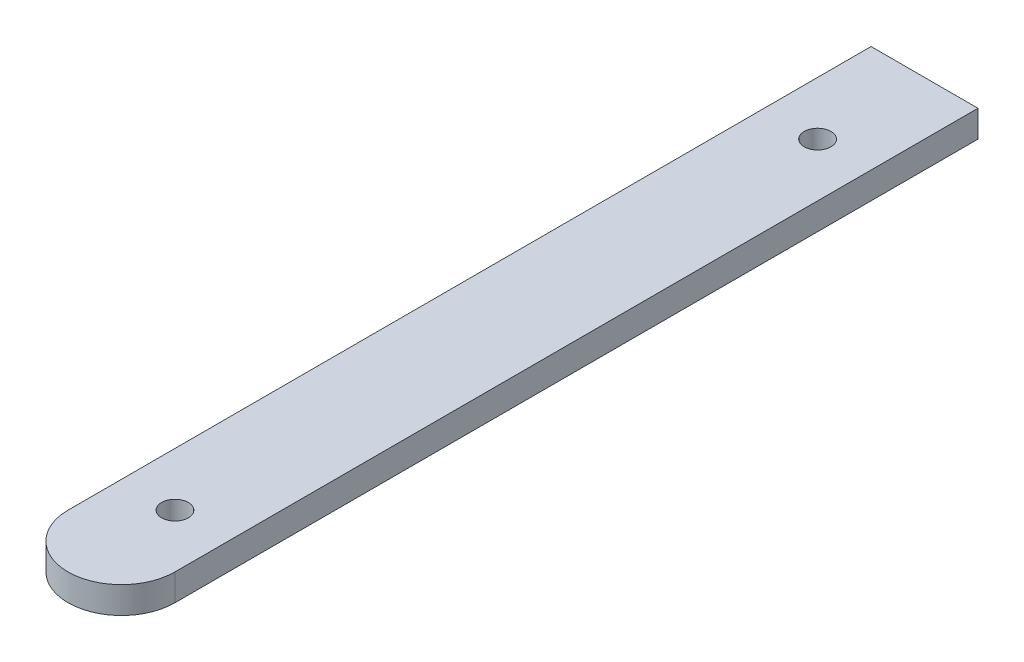
SolidWorks part; units mm, degrees
ref_plane "Front Plane" through (0, 0, 0) normal (0, 0, 1) x (1, 0, 0)
ref_plane "Top Plane" through (0, 0, 0) normal (0, 1, 0) x (1, 0, 0)
ref_plane "Right Plane" through (0, 0, 0) normal (1, 0, 0) x (0, 0, -1)
sketch "Sketch1" plane through (0, 0, 0) normal (0, 1, 0) x (1, 0, 0)
  line L1 (-6.4034, 28.0681) -> (18.9966, 28.0681)
  line L2 (-6.4034, 28.0681) -> (-6.4034, -175.3859)
  line L3 (-6.4034, -175.3859) -> (18.9966, -175.3859)
  line L4 (18.9966, 28.0681) -> (18.9966, -175.3859)
  circle A0 centre (6.2966, 2.6681) radius 3.175
  circle A1 centre (6.2966, -149.9859) radius 3.175
  point P8 (0, 0)
  dimension "D2" = 6.35
  dimension "D1" = 25.4
  dimension "D3" = 12.7
  dimension "D4" = 152.654
  dimension "D5" = 25.4
  dimension "D6" = 203.454
extrude "Boss-Extrude1" add sketch "Sketch1" along normal blind 6.35
fillet "Fillet1" 2 edges at (-6.4034, 3.175, 175.3859) (18.9966, 3.175, 175.3859) type full round first side face at (-6.4034, 3.175, 73.6589) second side face at (18.9966, 3.175, 73.6589) middle face at (6.2966, 3.175, 175.3859)
equation "\"width\"= 1in"
equation "\"t\"= 0.25in"
equation "\"D1@Sketch1\"=\"width\""
equation "\"D3@Sketch1\"=\"width\"/2"
equation "\"D1@Boss-Extrude1\"=\"t\""
